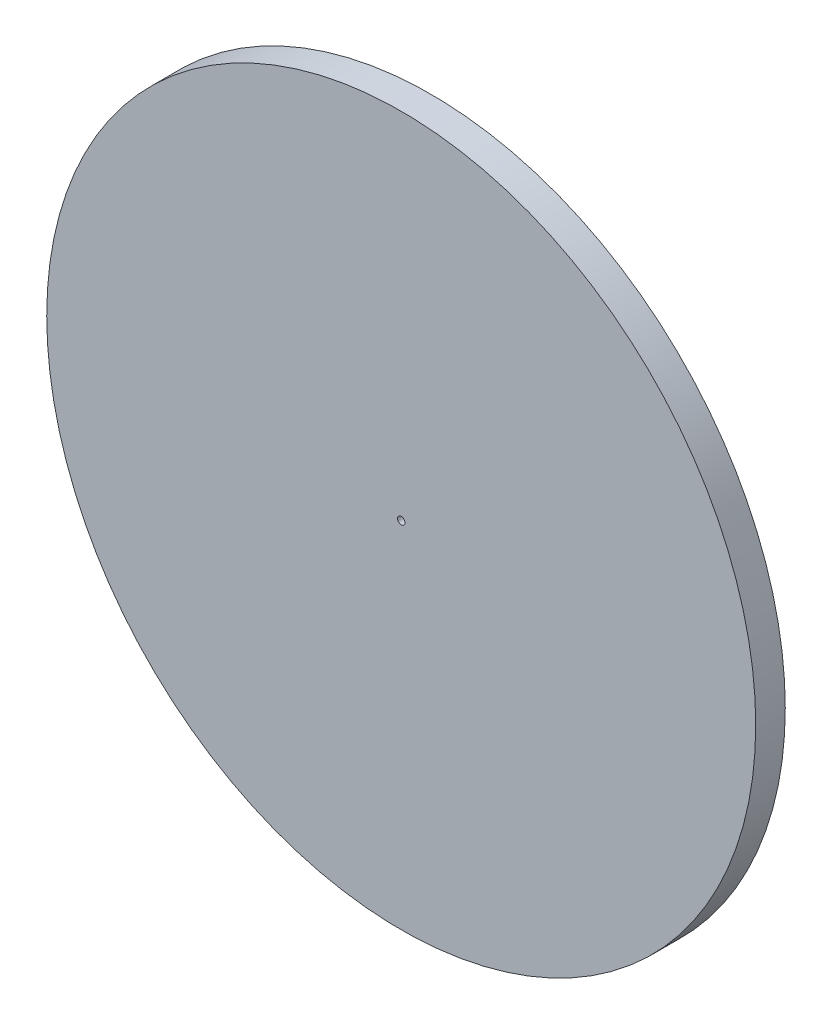
SolidWorks part; units mm, degrees
material "Maple"
ref_plane "Front Plane" through (0, 0, 0) normal (0, 0, 1) x (1, 0, 0)
ref_plane "Top Plane" through (0, 0, 0) normal (0, 1, 0) x (1, 0, 0)
ref_plane "Right Plane" through (0, 0, 0) normal (1, 0, 0) x (0, 0, -1)
sketch "Sketch1" plane through (0, 0, 0) normal (0, 0, 1) x (1, 0, 0)
  circle A0 centre (0, 0) radius 152.4
  dimension "D1" = 304.8
extrude "Boss-Extrude1" add sketch "Sketch1" along normal blind 12.7
sketch "Sketch2" plane through (0, 0, 0) normal (0, 0, -1) x (-1, 0, 0)
  circle A0 centre (0, 0) radius 1.5875
  dimension "D1" = 3.175
extrude "Cut-Extrude1" cut sketch "Sketch2" against normal through all
